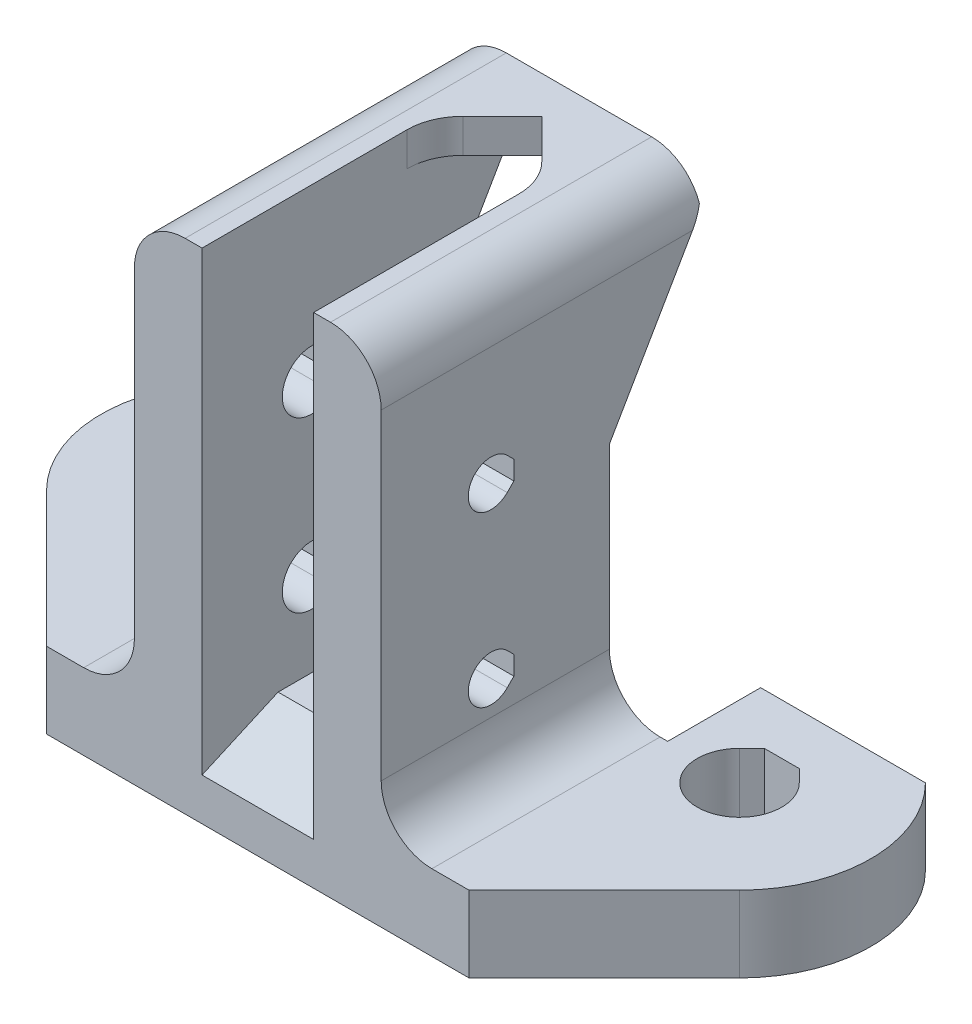
SolidWorks part; units mm, degrees
material "PET"
ref_plane "Front Plane" through (0, 0, 0) normal (0, 0, 1) x (1, 0, 0)
ref_plane "Top Plane" through (0, 0, 0) normal (0, 1, 0) x (1, 0, 0)
ref_plane "Right Plane" through (0, 0, 0) normal (1, 0, 0) x (0, 0, -1)
sketch "Sketch1" plane through (0, 0, 0) normal (0, 1, 0) x (1, 0, 0)
  line L0 (14.9975, 4) -> (0, 4) construction
  line L1 (-20.4975, -9.5) -> (20.4975, -9.5)
  line L2 (-20.4975, -9.5) -> (-20.4975, 9.5)
  line L3 (-20.4975, 9.5) -> (20.4975, 9.5)
  line L4 (20.4975, -9.5) -> (20.4975, 9.5)
  line L5 (-20.4975, -9.5) -> (20.4975, 9.5) construction
  line L6 (-20.4975, 9.5) -> (20.4975, -9.5) construction
  line L7 (0, 4) -> (-14.9975, 4) construction
  line L8 (20.4975, -1.5) -> (12.4975, -9.5)
  line L12 (-20.4975, -1.5) -> (-12.4975, -9.5)
  line L14 (-16.033, 6.5) -> (-16.7653, 5.7678)
  line L20 (-13.2297, 5.7678) -> (-13.962, 6.5)
  line L21 (-13.962, 6.5) -> (-16.033, 6.5)
  line L22 (-17.3202, 2.7872) -> (-16.5902, 2.0572) [skipped]
  line L23 (-17.4975, 4.7848) -> (-17.4975, 3.7525) [skipped]
  line L24 (-14.75, 1.5) -> (-13.7177, 1.5) [skipped]
  line L25 (-13.0547, 2.4073) -> (-12.3248, 3.1372) [skipped]
  line L26 (-12.4975, 4.2475) -> (-12.4975, 5.2798) [skipped]
  line L28 (13.962, 6.5) -> (13.2297, 5.7678)
  line L34 (16.7653, 5.7678) -> (16.033, 6.5)
  line L35 (16.033, 6.5) -> (13.962, 6.5)
  line L36 (13.0181, 2.4438) -> (13.7215, 1.7405) [skipped]
  line L37 (12.4975, 12.2993) -> (12.4975, 11.3046) [skipped]
  line L38 (15.6929, 1.5) -> (16.6876, 1.5) [skipped]
  line L39 (17.257, 2.724) -> (17.9603, 3.4273) [skipped]
  line L40 (17.4975, -11.3046) -> (17.4975, -10.3099) [skipped]
  arc A0 (13.2297, 5.7678) -> (16.7653, 5.7678) centre (14.9975, 4) ccw
  arc A1 (-16.7653, 5.7678) -> (-13.2297, 5.7678) centre (-14.9975, 4) ccw
  arc A2 (-20.4975, 9.5) -> (-20.4975, -1.5) centre (-14.9975, 4) ccw
  arc A3 (20.4975, 9.5) -> (20.4975, -1.5) centre (14.9975, 4) cw
  arc A4 (-16.7653, 5.7678) -> (-13.2297, 5.7678) centre (-14.9975, 4) ccw construction
  arc A5 (13.2297, 5.7678) -> (16.7653, 5.7678) centre (14.9975, 4) ccw construction
  point P0 (0, 0)
  dimension "D3" = 5
  dimension "D4" = 5.5
  dimension "D6" = 270
  dimension "D1" = 5.5
  dimension "D2" = 29.995
  dimension "D5" = 19
  dimension "D8" = 45
  dimension "D9" = 45
extrude "Boss-Extrude1" add sketch "Sketch1" along normal blind 4.5 contours A3 L4 | L1 L4 L3 L2 A1 A0 | L2 A2 region at (0, 0, -0.4101) region at (-21.4213, 0, -4) region at (21.4213, 0, -4)
sketch "Sketch2" plane through (0, 0, -9.5) normal (0, 0, -1) x (-1, 0, 0)
  line L2 (-3.3, 4.5) -> (-3.3, 27.5)
  line L4 (3.3, 4.5) -> (3.3, 27.5)
  line L6 (-7.3, 4.5) -> (-3.3, 4.5)
  line L11 (20.4975, 4.5) -> (-20.4975, 4.5) construction
  line L13 (3.3, 4.5) -> (7.3, 4.5)
  line L14 (-7.3, 29.5) -> (-7.3, 4.5)
  line L15 (-3.3, 27.5) -> (3.3, 27.5)
  line L17 (-7.3, 29.5) -> (7.3, 29.5)
  line L19 (7.3, 29.5) -> (7.3, 4.5)
  point P6 (0, 27.5)
  point P7 (0, 29.5)
  dimension "D1" = 6.6
  dimension "D2" = 4
  dimension "D3" = 23
  dimension "D4" = 2
extrude "Boss-Extrude2" add sketch "Sketch2" against normal through all contours L4 | L2 region at (5.3, 4.7895, -9.5)
sketch "Sketch4" plane through (0, 4.5, 0) normal (0, 1, 0) x (1, 0, 0)
  line L5 (3.3, -9.5) -> (3.3, 9.5) construction
  line L6 (-3.3, 9.5) -> (3.3, 9.5)
  line L7 (-3.3, 9.5) -> (-3.3, 4.7)
  line L8 (-3.3, 4.7) -> (3.3, 4.7)
  line L9 (3.3, 9.5) -> (3.3, 4.7)
  dimension "D1" = 4.8
sketch "Sketch15" [suppressed] plane through (0, 4.5, 0) normal (0, 1, 0) x (1, 0, 0)
  line L4 (3.3, 9.5) -> (-3.3, 9.5)
  line L5 (-3.3, 9.5) -> (-3.3, -9.5)
  line L6 (-3.3, -9.5) -> (3.3, -9.5)
  line L7 (3.3, -9.5) -> (3.3, 9.5)
  line L8 (3.3, 9.5) -> (-3.3, 9.5)
  line L9 (-3.3, 9.5) -> (-3.3, -9.5)
  line L10 (-3.3, -9.5) -> (3.3, -9.5)
  line L11 (3.3, -9.5) -> (3.3, 9.5)
  dimension "D1" = 0
extrude "Boss-Extrude6" [suppressed] add sketch "Sketch15" along normal offset from surface (1.9 mm away) 6.4
extrude "Boss-Extrude4" add sketch "Sketch4" along normal blind 2
sketch "Sketch5" plane through (0, 0, 9.5) normal (0, 0, 1) x (1, 0, 0)
  line L0 (-12.4975, 0) -> (12.4975, 0) construction
  line L1 (-3.3, 4.5) -> (3.3, 4.5)
  line L2 (-3.3, 4.5) -> (-3.3, 2.5)
  line L3 (-3.3, 2.5) -> (3.3, 2.5)
  line L4 (3.3, 4.5) -> (3.3, 2.5)
  line L7 (-3.3, 4.5) -> (-3.3, 27.5) construction
  point P5 (0, 2.5)
  dimension "D1" = 2
  dimension "D2" = 2.5
extrude "Cut-Extrude1" cut sketch "Sketch5" against normal blind 4.5
sketch "Sketch6" plane through (7.3, 0, 0) normal (1, 0, 0) x (0, 0, -1)
  line L0 (-9.5, 4.5) -> (9.5, 4.5) construction
  line L1 (-1.5, 4.5) -> (-9.5, 4.5) construction
  line L2 (-9.5, 29.5) -> (-9.5, 4.5) construction
  line L3 (-1.65, 20.0592) -> (-2.0454, 20.4546)
  line L9 (-2.0454, 18.5454) -> (-1.65, 18.9408)
  line L10 (-1.65, 18.9408) -> (-1.65, 20.0592)
  line L11 (-1.65, 10.0592) -> (-2.0454, 10.4546)
  line L17 (-2.0454, 8.5454) -> (-1.65, 8.9408)
  line L18 (-1.65, 8.9408) -> (-1.65, 10.0592)
  line L19 (-4.6031, 19.1939) -> (-4.3725, 18.9633) [skipped]
  line L20 (-4.35, 20.2648) -> (-4.35, 19.9387) [skipped]
  line L21 (-3.4138, 20.9954) -> (-3.6444, 20.7648) [skipped]
  line L22 (-2.2352, 20.85) -> (-2.5613, 20.85) [skipped]
  line L23 (-3.6073, 18.15) -> (-3.2812, 18.15) [skipped]
  line L24 (-3.3296, 7.9204) -> (-3.008, 7.5988) [skipped]
  line L25 (-4.35, 7.6) -> (-4.35, 7.1452) [skipped]
  line L26 (-3.3296, 11.0796) -> (-3.6512, 10.758) [skipped]
  line L27 (-1.75, 10.85) -> (-2.2048, 10.85) [skipped]
  line L28 (-1.75, 8.15) -> (-1.2952, 8.15) [skipped]
  arc A0 (-2.0454, 10.4546) -> (-2.0454, 8.5454) centre (-3, 9.5) ccw
  arc A1 (-2.0454, 20.4546) -> (-2.0454, 18.5454) centre (-3, 19.5) ccw
  arc A2 (-2.0454, 20.4546) -> (-2.0454, 18.5454) centre (-3, 19.5) ccw construction
  arc A3 (-2.0454, 10.4546) -> (-2.0454, 8.5454) centre (-3, 9.5) ccw construction
  dimension "D1" = 2.7
  dimension "D2" = 5
  dimension "D3" = 15
  dimension "D4" = 6.5
  dimension "D5" = 270
extrude "Cut-Extrude2" cut sketch "Sketch6" against normal up to next
sketch "Sketch8" plane through (-7.3, 0, 0) normal (-1, 0, 0) x (0, 0, 1)
  line L3 (1.25, 10.2249) -> (1.25, 8.7751)
  line L4 (1.25, 8.7751) -> (1.7626, 8.2626)
  line L10 (1.7626, 10.7374) -> (1.25, 10.2249)
  line L11 (1.9533, 7.75) -> (2.4636, 7.75) [skipped]
  line L12 (3.4973, 7.5224) -> (3.8581, 7.8833) [skipped]
  line L13 (4.75, 8.4533) -> (4.75, 8.9636) [skipped]
  line L14 (4.9776, 9.9973) -> (4.6167, 10.3581) [skipped]
  line L15 (4.0467, 11.25) -> (3.5364, 11.25) [skipped]
  line L16 (1.5, 4.5) -> (9.5, 4.5) construction
  line L17 (1.25, 20.2249) -> (1.25, 18.7751)
  line L18 (1.25, 18.7751) -> (1.7626, 18.2626)
  line L24 (1.7626, 20.7374) -> (1.25, 20.2249)
  line L25 (4.4071, 18.4322) -> (4.7468, 18.7719) [skipped]
  line L26 (4.75, 9.6876) -> (4.75, 10.168) [skipped]
  line L27 (12.7675, 12.2073) -> (12.4279, 12.547) [skipped]
  line L28 (0.8005, 21.25) -> (0.3201, 21.25) [skipped]
  line L29 (1.9117, 17.75) -> (2.392, 17.75) [skipped]
  arc A2 (1.7626, 8.2626) -> (1.7626, 10.7374) centre (3, 9.5) ccw
  arc A3 (2.0454, 8.5454) -> (2.0454, 10.4546) centre (3, 9.5) ccw construction
  arc A4 (1.7626, 18.2626) -> (1.7626, 20.7374) centre (3, 19.5) ccw
  dimension "D1" = 1.75
  dimension "D2" = 270
extrude "Cut-Extrude4" cut sketch "Sketch8" against normal up to next
sketch "Sketch9" plane through (0, 0, 9.5) normal (0, 0, 1) x (1, 0, 0)
  line L6 (7.3, 29.5) -> (-7.3, 29.5) construction
  line L7 (-3.3, 27.5) -> (3.3, 27.5)
  line L8 (-3.3, 27.5) -> (-3.3, 29.5)
  line L9 (-3.3, 29.5) -> (3.3, 29.5)
  line L10 (3.3, 27.5) -> (3.3, 29.5)
  line L11 (3.3, 2.5) -> (3.3, 27.5) construction
extrude "Cut-Extrude5" cut sketch "Sketch9" against normal offset from surface (16.8 mm away) 2.2 up to face at (0, 17, -9.5)
fillet "Fillet3" radius 3 2 edges at (-7.3, 4.5, 0) (7.3, 4.5, 0)
sketch "Sketch10" plane through (0, 0, 9.5) normal (0, 0, 1) x (1, 0, 0)
  line L0 (-12.4975, 0) -> (12.4975, 0) construction
  line L1 (-4.75, 0) -> (4.75, 0)
  line L2 (-4.75, 0) -> (-4.75, 4.5)
  line L3 (-4.75, 4.5) -> (4.75, 4.5)
  line L4 (4.75, 0) -> (4.75, 4.5)
  point P6 (0, 4.5)
  dimension "D1" = 4.5
  dimension "D2" = 9.5
extrude "Bolt head slot (X)" [suppressed] cut sketch "Sketch10" against normal up to surface (14.2 mm away)
sketch "Sketch13" [suppressed] plane through (0, 0, 0) normal (0, -1, 0) x (1, 0, 0)
  line L0 (-4.75, -4.7) -> (4.75, -4.7) construction
  line L1 (1.9675, -4.7) -> (4.75, -1.9175)
  line L7 (-4.75, -1.9175) -> (-1.9675, -4.7)
  line L8 (-1.9675, -4.7) -> (1.9675, -4.7)
  line L9 (4.75, -4.7) -> (4.75, 9.5) construction
  line L10 (-4.75, -4.7) -> (-4.75, 9.5) construction
  line L11 (4.75, 0.25) -> (4.75, 2.2175)
  line L12 (-4.75, 2.0175) -> (-4.75, 0.05)
  line L13 (3.4088, 3.3587) -> (2.0175, 4.75)
  line L14 (-1.9175, 4.85) -> (-3.3087, 3.4588)
  line L15 (2.0675, 4.8) -> (-1.8675, 4.8)
  line L16 (-4.75, -4.7) -> (-4.75, 9.5) construction
  line L17 (4.75, -4.7) -> (4.75, -1.9175)
  line L18 (-4.75, -4.7) -> (-4.75, -1.9175)
  line L19 (-4.75, -4.7) -> (-1.9675, -4.7)
  line L20 (1.9675, -4.7) -> (4.75, -4.7)
  line M12 (4.75, 9.5) -> (4.75, -4.7)
  line M13 (4.75, -4.7) -> (-4.75, -4.7)
  line M14 (-4.75, -4.7) -> (-4.75, 9.5)
extrude "Boss-Extrude5" [suppressed] add sketch "Sketch13" against normal up to surface (6.4 mm away) contours L7 M14 M13 | L1 M13 M12
fillet "Fillet5" [suppressed] radius 4.75
sketch "Sketch12" plane through (0, 0, 0) normal (0, -1, 0) x (1, 0, 0)
  line L0 (-20.4975, -9.5) -> (20.4975, -9.5) construction
  line L1 (-10.7475, -9.5) -> (10.7475, -9.5)
  line L2 (-10.7475, -9.5) -> (-10.7475, -4)
  line L3 (-10.7475, -4) -> (10.7475, -4)
  line L4 (10.7475, -9.5) -> (10.7475, -4)
  arc A0 (16.7653, -5.7678) -> (13.2297, -5.7678) centre (14.9975, -4) ccw construction
  point P6 (0, -4)
  dimension "D1" = 5.5
  dimension "D2" = 4.25
extrude "Cut-Extrude8" cut sketch "Sketch12" against normal blind 18
fillet "Fillet7" radius 3 2 edges at (7.3, 29.5, 0) (-7.3, 29.5, 0)
chamfer "Chamfer2" distance 4.5 distance2 2 1 edges at (0, 2.5, 5) first distance on face at (0, 2.5, 7.25)
chamfer "Chamfer3" distance 3.3 angle 45 2 edges at (-3.3, 28.5, -7.3) (3.3, 28.5, -7.3)
fillet "Fillet8" radius 3.3 2 edges at (3.3, 28.5, -4) (-3.3, 28.5, -4)
sketch "Sketch14" [suppressed] plane through (0, 0, -9.5) normal (0, 0, -1) x (-1, 0, 0)
  line L8 (4.3, 29.5) -> (-4.3, 29.5)
  line L9 (-7.3, 26.5) -> (-7.3, 18)
  line L10 (-7.3, 18) -> (-3.3, 18)
  line L11 (-3.3, 18) -> (-3.3, 27.5)
  line L12 (-3.3, 27.5) -> (3.3, 27.5)
  line L13 (3.3, 27.5) -> (3.3, 18)
  line L14 (3.3, 18) -> (7.3, 18)
  line L15 (7.3, 18) -> (7.3, 26.5)
  line L16 (4.3, 29.5) -> (-4.3, 29.5)
  line L17 (-7.3, 26.5) -> (-7.3, 18)
  line L18 (-7.3, 18) -> (-3.3, 18)
  line L19 (-3.3, 18) -> (-3.3, 27.5)
  line L20 (-3.3, 27.5) -> (3.3, 27.5)
  line L21 (3.3, 27.5) -> (3.3, 18)
  line L22 (3.3, 18) -> (7.3, 18)
  line L23 (7.3, 18) -> (7.3, 26.5)
  arc A2 (-4.3, 29.5) -> (-7.3, 26.5) centre (-4.3, 26.5) ccw
  arc A3 (7.3, 26.5) -> (4.3, 29.5) centre (4.3, 26.5) ccw
  arc A4 (-4.3, 29.5) -> (-7.3, 26.5) centre (-4.3, 26.5) ccw
  arc A5 (7.3, 26.5) -> (4.3, 29.5) centre (4.3, 26.5) ccw
  dimension "D1" = 0
extrude "Cut-Extrude9" [suppressed] cut sketch "Sketch14" against normal blind 3.5
chamfer "Chamfer4" distance 9.5 distance2 5.5 2 edges at (-5.3, 18, -9.5) (5.3, 18, -9.5) first distance on face at (0, 24.0243, -9.5)
chamfer "Chamfer5" [suppressed] distance 2 distance2 9.5
